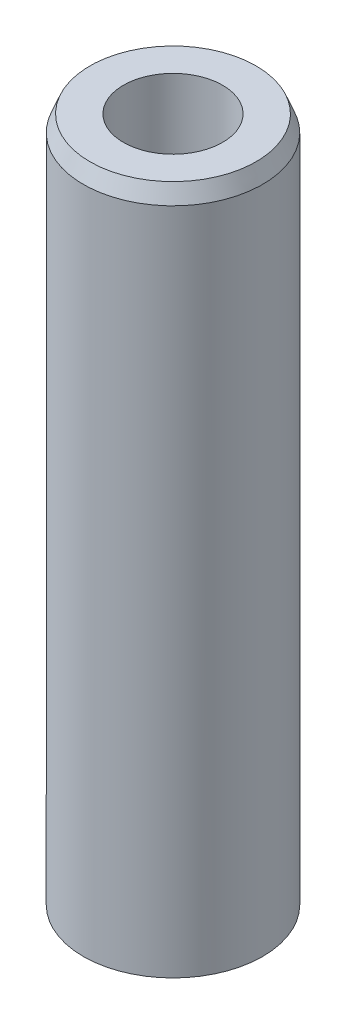
SolidWorks part; units mm, degrees
ref_plane "Front Plane" through (0, 0, 0) normal (0, 0, 1) x (1, 0, 0)
ref_plane "Top Plane" through (0, 0, 0) normal (0, 1, 0) x (1, 0, 0)
ref_plane "Right Plane" through (0, 0, 0) normal (1, 0, 0) x (0, 0, -1)
sketch "Sketch1" plane through (0, 0, 0) normal (0, 1, 0) x (1, 0, 0)
  circle A0 centre (0, 0) radius 10
  dimension "SHAFT_OD" = 20
extrude "Boss-Extrude1" add sketch "Sketch1" along normal blind 77.1552
sketch "Sketch2" plane through (0, 0, 0) normal (0, 1, 0) x (1, 0, 0)
  circle A0 centre (0, 0) radius 5.531
  dimension "BORE_D" = 11.0621
extrude "Cut-Extrude1" cut sketch "Sketch2" along normal through all
chamfer "Chamfer1" distance 1.8251 angle 21.865 2 edges at (0, 77.1552, 10) (0, 0, 10) first distance on face at (0, 77.1552, 10) first distance on face at (0, 0, 5.531)
